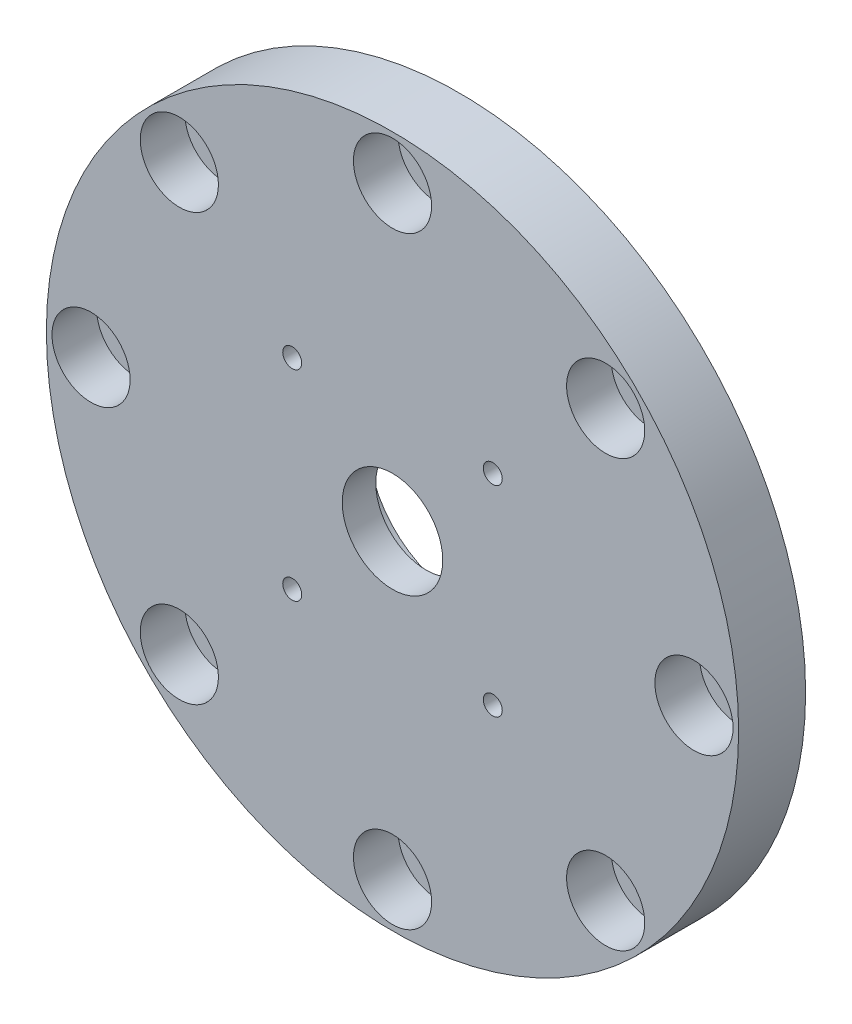
SolidWorks part; units mm, degrees
ref_plane "Front Plane" through (0, 0, 0) normal (0, 0, 1) x (1, 0, 0)
ref_plane "Top Plane" through (0, 0, 0) normal (0, 1, 0) x (1, 0, 0)
ref_plane "Right Plane" through (0, 0, 0) normal (1, 0, 0) x (0, 0, -1)
sketch "Sketch1" plane through (0, 0, 0) normal (0, 0, 1) x (1, 0, 0)
  line L11 (0, 0) -> (8.9803, 8.9803) construction
  line L17 (0, 0) -> (-27, 0) construction
  circle A2 centre (0, 0) radius 4.5
  circle A3 centre (0, 0) radius 12.7 construction
  circle A11 centre (8.9803, 8.9803) radius 0.85
  circle A12 centre (8.9803, -8.9803) radius 0.85
  circle A13 centre (-8.9803, -8.9803) radius 0.85
  circle A14 centre (-8.9803, 8.9803) radius 0.85
  circle A33 centre (0, 0) radius 24 construction
  circle A34 centre (0, 0) radius 31
  circle A35 centre (-27, 0) radius 1.55
  circle A36 centre (-19.0919, 19.0919) radius 1.55
  circle A37 centre (0, 27) radius 1.55
  circle A38 centre (19.0919, 19.0919) radius 1.55
  circle A39 centre (27, 0) radius 1.55
  circle A40 centre (19.0919, -19.0919) radius 1.55
  circle A41 centre (0, -27) radius 1.55
  circle A42 centre (-19.0919, -19.0919) radius 1.55
  point P7 (0, 0)
  point P10 (0, 0)
  point P12 (0, 0)
  point P16 (0, 0)
  point P17 (0, 0)
  point P20 (0, 0)
  point P30 (0, 0)
  point P39 (0, 0)
  point P47 (0, 0)
  point P64 (0, 0)
  dimension "D1" = 4
extrude "Boss-Extrude2" add sketch "Sketch1" along normal blind 6
sketch "Sketch5" plane through (0, 0, 0) normal (0, 0, -1) x (-1, 0, 0)
  circle A0 centre (0, 0) radius 8.2
extrude "Cut-Extrude3" cut sketch "Sketch5" against normal blind 3
sketch "Sketch6" plane through (0, 0, 6) normal (0, 0, 1) x (1, 0, 0)
  circle A7 centre (0, 27) radius 3.5
  circle A8 centre (19.0919, 19.0919) radius 3.5
  circle A9 centre (27, 0) radius 3.5
  circle A10 centre (19.0919, -19.0919) radius 3.5
  circle A11 centre (0, -27) radius 3.5
  circle A12 centre (-19.0919, -19.0919) radius 3.5
  circle A13 centre (-27, 0) radius 3.5
  circle A14 centre (-19.0919, 19.0919) radius 3.5
  point P11 (-3.75, 3.75)
  point P29 (0, 0)
  point P31 (0, 0)
  dimension "D2" = 8
extrude "Cut-Extrude4" cut sketch "Sketch6" against normal blind 4
sketch "Sketch7" plane through (0, 0, 0) normal (0, 0, -1) x (-1, 0, 0)
  line L0 (-8.9803, 11.3403) -> (-8.9803, 6.6203) construction
  line L1 (-11.0241, 7.8003) -> (-6.9364, 10.1603) construction
  line L2 (-6.9364, 7.8003) -> (-11.0241, 10.1603) construction
  line L3 (-6.9364, 10.1603) -> (-8.9803, 11.3403)
  line L4 (-8.9803, 11.3403) -> (-11.0241, 10.1603)
  line L5 (-11.0241, 10.1603) -> (-11.0241, 7.8003)
  line L6 (-11.0241, 7.8003) -> (-8.9803, 6.6203)
  line L7 (-8.9803, 6.6203) -> (-6.9364, 7.8003)
  line L8 (-6.9364, 7.8003) -> (-6.9364, 10.1603)
  line L9 (10.1603, 6.9364) -> (11.3403, 8.9803)
  line L10 (11.3403, 8.9803) -> (10.1603, 11.0241)
  line L11 (10.1603, 11.0241) -> (7.8003, 11.0241)
  line L12 (7.8003, 11.0241) -> (6.6203, 8.9803)
  line L13 (6.6203, 8.9803) -> (7.8003, 6.9364)
  line L14 (7.8003, 6.9364) -> (10.1603, 6.9364)
  line L15 (11.3403, 8.9803) -> (6.6203, 8.9803) construction
  line L16 (7.8003, 11.0241) -> (10.1603, 6.9364) construction
  line L17 (7.8003, 6.9364) -> (10.1603, 11.0241) construction
  line L18 (6.9364, -10.1603) -> (8.9803, -11.3403)
  line L19 (8.9803, -11.3403) -> (11.0241, -10.1603)
  line L20 (11.0241, -10.1603) -> (11.0241, -7.8003)
  line L21 (11.0241, -7.8003) -> (8.9803, -6.6203)
  line L22 (8.9803, -6.6203) -> (6.9364, -7.8003)
  line L23 (6.9364, -7.8003) -> (6.9364, -10.1603)
  line L24 (8.9803, -11.3403) -> (8.9803, -6.6203) construction
  line L25 (11.0241, -7.8003) -> (6.9364, -10.1603) construction
  line L26 (6.9364, -7.8003) -> (11.0241, -10.1603) construction
  line L27 (-10.1603, -6.9364) -> (-11.3403, -8.9803)
  line L28 (-11.3403, -8.9803) -> (-10.1603, -11.0241)
  line L29 (-10.1603, -11.0241) -> (-7.8003, -11.0241)
  line L30 (-7.8003, -11.0241) -> (-6.6203, -8.9803)
  line L31 (-6.6203, -8.9803) -> (-7.8003, -6.9364)
  line L32 (-7.8003, -6.9364) -> (-10.1603, -6.9364)
  line L33 (-11.3403, -8.9803) -> (-6.6203, -8.9803) construction
  line L34 (-7.8003, -11.0241) -> (-10.1603, -6.9364) construction
  line L35 (-7.8003, -6.9364) -> (-10.1603, -11.0241) construction
  circle A0 centre (-8.9803, 8.9803) radius 2.36 construction
  circle A1 centre (8.9803, 8.9803) radius 2.36 construction
  circle A2 centre (8.9803, -8.9803) radius 2.36 construction
  circle A3 centre (-8.9803, -8.9803) radius 2.36 construction
  point P8 (-8.9803, 8.9803)
  point P11 (-8.9803, 8.9803)
  point P20 (8.9803, 8.9803)
  point P23 (8.9803, 8.9803)
  point P30 (8.9803, -8.9803)
  point P33 (8.9803, -8.9803)
  point P40 (-8.9803, -8.9803)
  point P43 (-8.9803, -8.9803)
  point P44 (0, 0)
  dimension "D1" = 4
extrude "Cut-Extrude5" cut sketch "Sketch7" against normal blind 2
